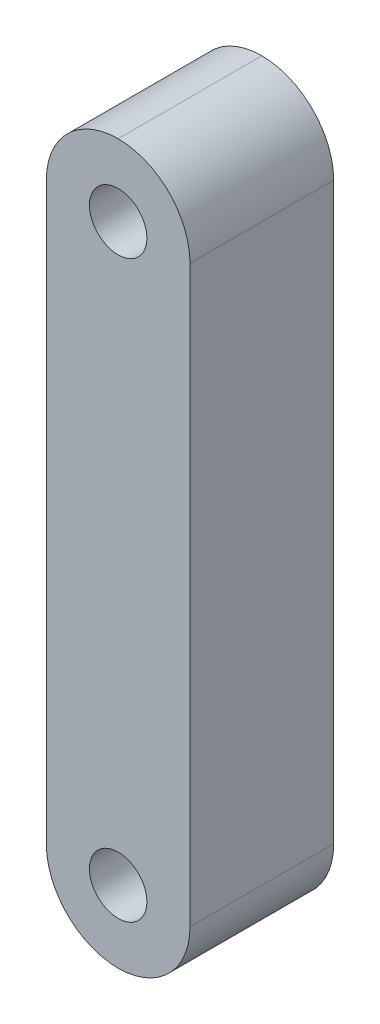
SolidWorks part; units mm, degrees
ref_plane "Front" through (0, 0, 0) normal (0, 0, 1) x (1, 0, 0)
ref_plane "Top" through (0, 0, 0) normal (0, 1, 0) x (1, 0, 0)
ref_plane "Right" through (0, 0, 0) normal (1, 0, 0) x (0, 0, -1)
sketch "Esquisse1" plane through (0, 0, 0) normal (0, 0, 1) x (1, 0, 0)
  line L1 (0, 0) -> (10, 0)
  line L2 (0, 0) -> (0, 50)
  line L3 (0, 50) -> (10, 50)
  line L4 (10, 0) -> (10, 50)
  dimension "D1" = 10
  dimension "D2" = 50
extrude "Boss.-Extru.1" add sketch "Esquisse1" along normal blind 10
sketch "Esquisse2" plane through (0, 0, 10) normal (0, 0, 1) x (1, 0, 0)
  line L0 (5, 50) -> (5, 45) construction
  line L1 (10, 50) -> (0, 50) construction
  line L2 (0, 0) -> (10, 0) construction
  line L3 (5, 5) -> (5, 0) construction
  circle A1 centre (5, 45) radius 2
  circle A2 centre (5, 5) radius 2
  point P4 (5, 75)
  point P11 (5, 0)
  dimension "D2" = 5
  dimension "D3" = 4
  dimension "D4" = 4
  dimension "D5" = 5
extrude "Enlèv. mat.-Extru.1" cut sketch "Esquisse2" against normal up to vertex (10 mm away) up to point (0, 50, 0)
fillet "Congé1" radius 5 4 edges at (10, 50, 5) (0, 50, 5) (10, 0, 5) (0, 0, 5)
